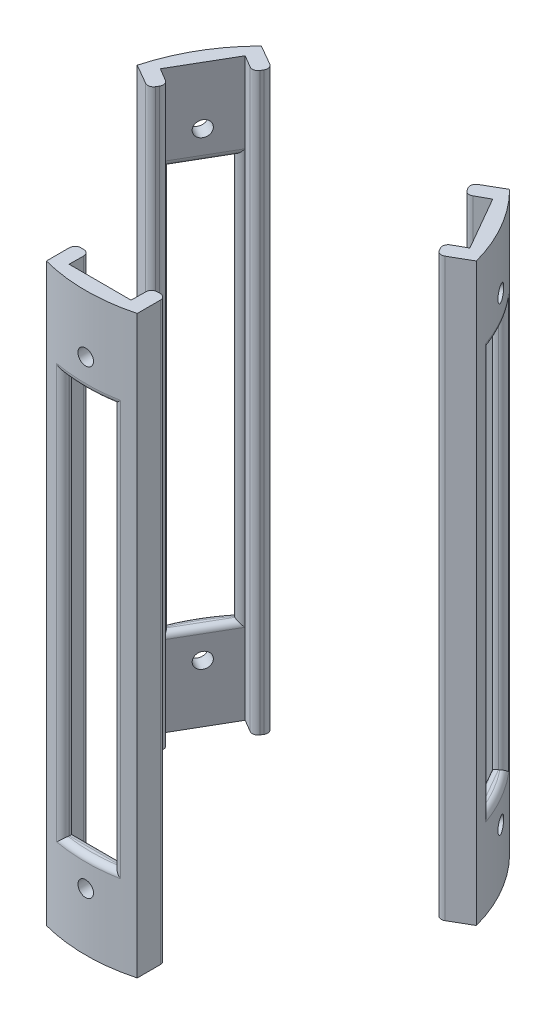
SolidWorks part; units mm, degrees
material "ABS"
ref_plane "Front Plane" through (0, 0, 0) normal (0, 0, 1) x (1, 0, 0)
ref_plane "Top Plane" through (0, 0, 0) normal (0, 1, 0) x (1, 0, 0)
ref_plane "Right Plane" through (0, 0, 0) normal (1, 0, 0) x (0, 0, -1)
sketch "Sketch1" plane through (0, 0, 0) normal (0, 1, 0) x (1, 0, 0)
  line L0 (0, 0) -> (0, -30.5) construction
  line L1 (0, 0) -> (26.4138, 15.25) construction
  line L2 (0, 0) -> (-26.4138, 15.25) construction
  line L3 (0, 0) -> (29.4607, 7.894) construction
  line L4 (0, 0) -> (21.5668, 21.5668) construction
  line L5 (21.5668, 21.5668) -> (29.4607, 7.894) construction
  line L6 (21.5668, 21.5668) -> (17.2366, 19.0668)
  line L7 (29.4607, 7.894) -> (25.1306, 5.394)
  line L8 (17.2366, 19.0668) -> (18.4866, 16.9017)
  line L9 (25.1306, 5.394) -> (23.9083, 7.5748)
  line L10 (18.4866, 16.9017) -> (21.5668, 18.6313)
  line L11 (23.9083, 7.5748) -> (26.9475, 9.2782)
  line L12 (21.5668, 18.6313) -> (26.9475, 9.2782)
  line L13 (-5.3942, -24.4926) -> (-5.4386, -27.9763)
  line L14 (-7.894, -24.4607) -> (-5.3942, -24.4926)
  line L15 (-7.894, -29.4607) -> (-7.894, -24.4607)
  line L16 (5.394, -24.4607) -> (5.3518, -27.993)
  line L17 (5.3518, -27.993) -> (-5.4386, -27.9763)
  line L18 (7.894, -24.4607) -> (5.394, -24.4607)
  line L19 (7.894, -29.4607) -> (7.894, -24.4607)
  line L20 (-18.5141, 16.9178) -> (-21.5089, 18.6981)
  line L21 (-17.2366, 19.0668) -> (-18.5141, 16.9178)
  line L22 (-21.5668, 21.5668) -> (-17.2366, 19.0668)
  line L23 (-23.8806, 7.559) -> (-26.9185, 9.3617)
  line L24 (-26.9185, 9.3617) -> (-21.5089, 18.6981)
  line L25 (-25.1306, 5.394) -> (-23.8806, 7.559)
  line L26 (-29.4607, 7.894) -> (-25.1306, 5.394)
  circle A0 centre (0, 0) radius 30.5
  circle A1 centre (0, 0) radius 28.5
  point P4 (20.1525, 20.1525)
  point P10 (27.5289, 7.3763)
  point P35 (0, 0)
  dimension "D1" = 61
  dimension "D2" = 57
  dimension "D3" = 120
  dimension "D4" = 120
  dimension "D5" = 15
  dimension "D6" = 15
  dimension "D7" = 5
  dimension "D8" = 90
  dimension "D9" = 5
  dimension "D10" = 90
  dimension "D11" = 2.5
  dimension "D12" = 2.5
  dimension "D13" = 3
extrude "Boss-Extrude1" add sketch "Sketch1" along normal blind 100 contours A1 L15 A0 L19 | L15 A1 L13 L14 | L16 A1 L19 L18 | L17 A1 region at (0, 0, 29.1401) region at (6.5943, 0, 26.094) region at (-6.6191, 0, 26.0884) region at (-0.0437, 0, 28.1909)
sketch "Sketch2" plane through (-0.0434, 0, 27.9846) normal (0.0016, 0, -1) x (-1, 0, -0.0016)
  line L0 (-5.3952, 100) -> (5.3952, 100) construction
  line L1 (-5.3952, 0) -> (5.3952, 0) construction
  circle A0 centre (0, 90) radius 1.35
  circle A1 centre (0, 10) radius 1.35
  dimension "D1" = 2.7
  dimension "D2" = 10
  dimension "D3" = 2.7
  dimension "D4" = 10
extrude "Cut-Extrude1" cut sketch "Sketch2" against normal blind 100
sketch "Sketch3" plane through (-0.0434, 0, 27.9846) normal (0.0016, 0, -1) x (-1, 0, -0.0016)
  line L0 (-5.3952, 100) -> (-5.3952, 0) construction
  line L1 (-4.3952, 85) -> (4.3562, 85)
  line L2 (-4.3952, 85) -> (-4.3952, 15)
  line L3 (-4.3952, 15) -> (4.3562, 15)
  line L4 (4.3562, 85) -> (4.3562, 15)
  line L5 (5.3562, 100) -> (5.3562, 0) construction
  line L6 (-4.3952, 85) -> (4.3562, 76.2486)
  line L7 (4.3562, 76.2486) -> (-4.3952, 67.4972)
  line L8 (-4.3952, 67.4972) -> (4.3562, 58.7458)
  line L9 (4.3562, 58.7458) -> (-4.3952, 50)
  line L10 (-4.3952, 50) -> (4.3562, 41.243)
  line L11 (4.3562, 41.243) -> (-4.3952, 32.4972)
  line L12 (-4.3952, 32.4972) -> (4.3562, 23.7402)
  line L13 (4.3562, 23.7402) -> (-4.3952, 15)
  line L14 (-2.3952, 85) -> (4.3562, 78.2486)
  line L15 (-4.3952, 83) -> (2.3562, 76.2486)
  line L16 (2.3562, 76.2486) -> (-4.3952, 69.4972)
  line L17 (-4.3952, 65.4972) -> (2.3562, 58.7458)
  line L18 (-4.3952, 48) -> (2.3562, 41.243)
  line L19 (-4.3952, 30.4972) -> (2.3562, 23.7402)
  line L20 (2.3562, 58.7458) -> (-4.3952, 51.9944)
  line L21 (2.3562, 41.243) -> (-4.3952, 34.4916)
  line L22 (2.3562, 23.7402) -> (-4.3952, 16.9888)
  line L23 (4.3562, 74.2486) -> (-2.3952, 67.3478)
  line L24 (4.3562, 56.7458) -> (-2.3952, 50)
  line L25 (4.3562, 39.243) -> (-2.3952, 32.4972)
  line L26 (-2.3952, 67.3478) -> (4.3562, 60.5964)
  line L27 (-2.3952, 50) -> (4.3562, 43.2486)
  line L28 (-2.3952, 32.4972) -> (4.3562, 25.7458)
  line L29 (4.3562, 21.7402) -> (-2.3952, 15)
  circle A0 centre (0, 90) radius 1.35 construction
  circle A1 centre (0, 10) radius 1.35 construction
  dimension "D1" = 1
  dimension "D2" = 1
  dimension "D3" = 5
  dimension "D4" = 5
  dimension "D5" = 2
  dimension "D6" = 2
  dimension "D7" = 2
  dimension "D8" = 2
  dimension "D9" = 2
  dimension "D10" = 2
  dimension "D11" = 2
  dimension "D12" = 2
  dimension "D13" = 2
  dimension "D14" = 2
  dimension "D15" = 2
  dimension "D16" = 2
extrude "Cut-Extrude5" cut sketch "Sketch3" against normal blind 100 contours L16 L15 L2 | L23 L26 L4 | L20 L17 L2 | L24 L27 L4 | L21 L18 L2 | L25 L28 L4 | L22 L19 L2 | L1 L14 L4 | L4 L29 L3 | L15 L16 L2 L7 L6 | L14 L1 L6 L4 | L26 L23 L4 L7 L8 | L17 L20 L2 L9 L8 | L27 L24 L4 L9 L10 | L18 L21 L2 L11 L10 | L28 L25 L4 L11 L12 | L19 L22 L2 L13 L12 | L29 L4 L13 L3 region at (0.1145, 80.4859, 27.9849) region at (-0.5024, 81.1028, 27.9839) region at (-2.1491, 82.7495, 27.9814) region at (2.1013, 76.2486, 27.988) region at (-4.2039, 75.2486, 27.9782) region at (-2.1491, 67.3976, 27.9814) region at (0.1144, 62.9832, 27.9849) region at (2.1013, 58.7458, 27.988) region at (-4.2039, 57.7458, 27.9782) region at (-2.1491, 49.9981, 27.9814) region at (0.1145, 45.4832, 27.9849) region at (2.1013, 41.2449, 27.988) region at (-4.2039, 40.243, 27.9782) region at (-2.1491, 32.4954, 27.9814) region at (0.1145, 27.9804, 27.9849) region at (2.1013, 23.7421, 27.988) region at (-0.5033, 18.8926, 27.9839) region at (-2.1491, 17.2467, 27.9814)
sketch "Sketch5" plane through (0, 0, 0) normal (0, 1, 0) x (1, 0, 0)
  line L0 (0, 0) -> (0, 32.3542) construction
ref_axis "Axis1" through (0, -5, 0) along (0, 1, 0)
pattern_circular "CirPattern3" count 3 every 120 about axis through (0, -5, 0) along (0, 1, 0) of bodies 105
fillet "Fillet1" radius 1 12 edges at (-25.1306, 50, -5.394) (-23.8806, 50, -7.559) (-18.5141, 50, -16.9178) (-17.2366, 50, -19.0668) (-26.4, 85, -15.2739) (-24.2235, 85, -14.013) (-26.4172, 50, -10.227) (-28.3181, 50, -11.3284) (-24.2235, 15, -14.013) (-26.4, 15, -15.2739) (-22.0298, 50, -17.7991) (-23.9356, 50, -18.9034)
fillet "Fillet2" radius 1 12 edges at (18.4866, 50, -16.9017) (17.2366, 50, -19.0668) (25.1306, 50, -5.394) (23.9083, 50, -7.5748) (26.4276, 85, -15.2261) (24.2474, 85, -13.9716) (23.9698, 50, -18.86) (22.0654, 50, -17.7645) (24.2474, 15, -13.9716) (26.4276, 15, -15.2261) (26.4293, 50, -10.1788) (28.3386, 50, -11.2771)
fillet "Fillet3" radius 1 12 edges at (-7.894, 50, 24.4607) (-5.3942, 50, 24.4926) (5.394, 50, 24.4607) (7.894, 50, 24.4607) (4.3484, 50, 30.1884) (4.3518, 50, 27.9915) (-0.0276, 15, 30.5) (-0.0239, 15, 27.9847) (-0.0276, 85, 30.5) (-0.0239, 85, 27.9847) (-4.403, 50, 30.1805) (-4.3996, 50, 27.9779)
